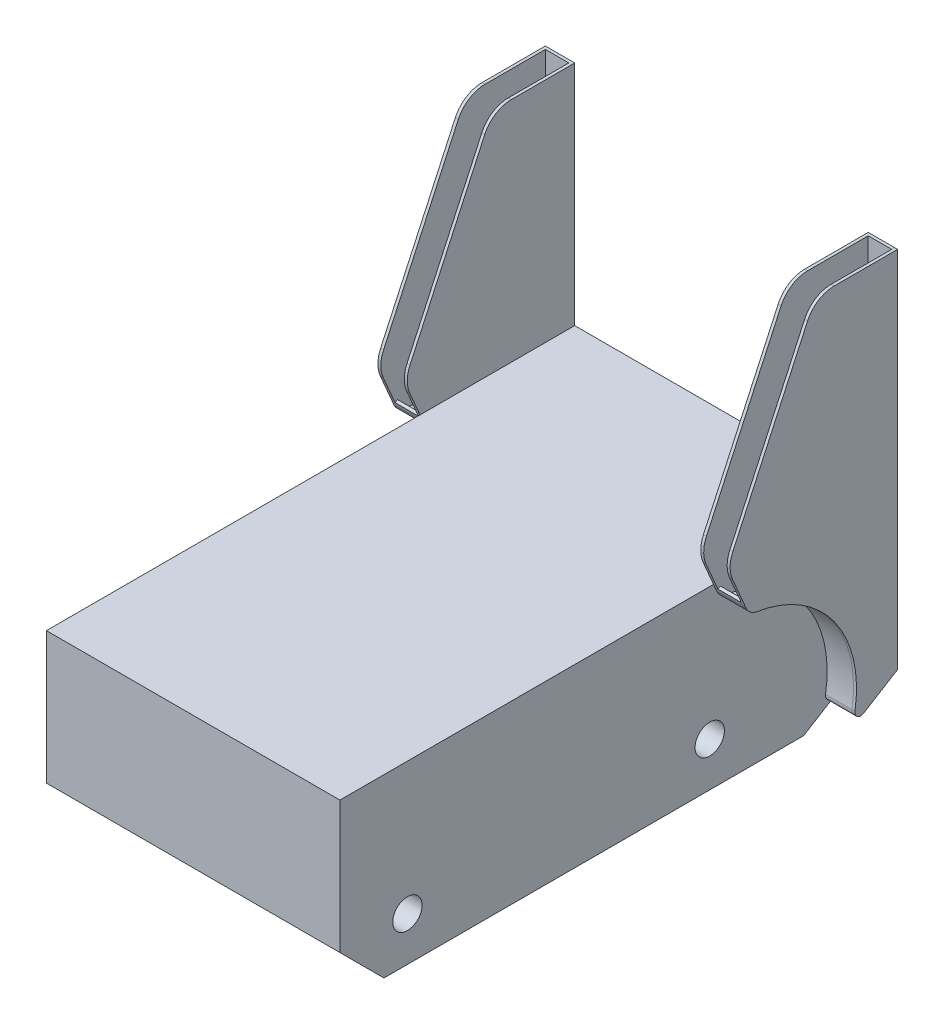
SolidWorks part; units mm, degrees
ref_plane "Front Plane" through (0, 0, 0) normal (0, 0, 1) x (1, 0, 0)
ref_plane "Top Plane" through (0, 0, 0) normal (0, 1, 0) x (1, 0, 0)
ref_plane "Right Plane" through (0, 0, 0) normal (1, 0, 0) x (0, 0, -1)
sketch "Sketch2" plane through (0, 0, 0) normal (1, 0, 0) x (0, 0, -1)
  line L0 (-750, 0) -> (680, 0)
  line L1 (680, 0) -> (900, 135)
  line L2 (900, 135) -> (900, 600)
  line L3 (900, 600) -> (-900, 600)
  line L4 (-900, 600) -> (-900, 150)
  line L5 (-900, 150) -> (-750, 0)
  circle A0 centre (-670, 150) radius 50
  circle A1 centre (360, 150) radius 50
  point P13 (0, 0)
  point P14 (0, 0)
  point P15 (204.7634, 67.3548)
  dimension "D8" = 100
  dimension "D1" = 1800
  dimension "D2" = 150
  dimension "D3" = 150
  dimension "D4" = 220
  dimension "D5" = 135
  dimension "D6" = 600
  dimension "D7" = 900
  dimension "D9" = 1030
  dimension "D10" = 150
  dimension "D11" = 540
extrude "Boss-Extrude1" add sketch "Sketch2" along normal mid plane 1000
sketch "Sketch3" plane through (500, 0, 0) normal (1, 0, 0) x (0, 0, -1)
  line L0 (900, 135) -> (900, 1375)
  line L1 (900, 1375) -> (684.0464, 1375)
  line L2 (593.213, 1316.8244) -> (338.5875, 763.8338)
  line L3 (337.5065, 682.6174) -> (383.6781, 574.8835)
  line L4 (900, 135) -> (784.8142, 64.3178)
  line L5 (680, 0) -> (900, 135) construction
  arc A0 (784.8142, 64.3178) -> (754.6227, 84.6326) centre (774.3539, 81.3643) cw
  arc A1 (754.6227, 84.6326) -> (421.8981, 545.1818) centre (360, 150) ccw
  circle A2 centre (360, 150) radius 50 construction
  arc A3 (383.6781, 574.8835) -> (421.8981, 545.1818) centre (429.6354, 594.5795) ccw
  arc A4 (684.0464, 1375) -> (593.213, 1316.8244) centre (684.0464, 1275) ccw
  arc A5 (338.5875, 763.8338) -> (337.5065, 682.6174) centre (429.421, 722.0093) ccw
  point P12 (0, 0)
  point P17 (395, 548.4658)
  point P20 (620, 1375)
  point P23 (320, 723.4658)
  dimension "D5" = 20
  dimension "D6" = 400
  dimension "D8" = 50
  dimension "D9" = 100
  dimension "D10" = 100
  dimension "D1" = 1240
  dimension "D2" = 280
  dimension "D3" = 175
  dimension "D4" = 75
  dimension "D7" = 35
extrude "Boss-Extrude2" add sketch "Sketch3" along normal blind 10 separate body
sketch "Sketch4" plane through (510, 0, 0) normal (1, 0, 0) x (0, 0, -1)
  line L0 (372.9139, 600) -> (383.6781, 574.8835) construction
  line L1 (382.1054, 603.9392) -> (392.8696, 578.8227) construction
  line L2 (377.6282, 589) -> (386.8197, 592.9392)
  line L3 (900, 135) -> (900, 1375) construction
  line L4 (784.8142, 64.3178) -> (900, 135) construction
  line L5 (372.9139, 600) -> (383.6781, 574.8835) construction
  line L6 (377.6282, 589) -> (383.6781, 574.8835)
  line L7 (784.8142, 64.3178) -> (900, 135)
  line L8 (900, 135) -> (900, 1375)
  line L9 (386.8197, 592.9392) -> (392.8696, 578.8227)
  line L10 (779.584, 72.841) -> (890, 140.5963)
  line L11 (890, 140.5963) -> (890, 1375)
  line L12 (890, 1375) -> (900, 1375)
  line L13 (900, 600) -> (-900, 600) construction
  arc A2 (754.6227, 84.6326) -> (784.8142, 64.3178) centre (774.3539, 81.3643) ccw construction
  arc A3 (754.6227, 84.6326) -> (421.8981, 545.1818) centre (360, 150) ccw construction
  arc A4 (383.6781, 574.8835) -> (421.8981, 545.1818) centre (429.6354, 594.5795) ccw construction
  arc A5 (383.6781, 574.8835) -> (421.8981, 545.1818) centre (429.6354, 594.5795) ccw
  arc A6 (754.6227, 84.6326) -> (421.8981, 545.1818) centre (360, 150) ccw
  arc A7 (754.6227, 84.6326) -> (784.8142, 64.3178) centre (774.3539, 81.3643) ccw
  arc A8 (392.8696, 578.8227) -> (423.4456, 555.0613) centre (429.6354, 594.5795) ccw
  arc A9 (764.4883, 82.9984) -> (423.4456, 555.0613) centre (360, 150) ccw
  arc A10 (764.4883, 82.9984) -> (779.584, 72.841) centre (774.3539, 81.3643) ccw
  dimension "D2" = 11
  dimension "D1" = 10
extrude "Boss-Extrude3" add sketch "Sketch4" along normal blind 80
extrude "Boss-Extrude4" add sketch "Sketch3<2>" along normal blind 10 from offset 90
sketch "Sketch3<2>" plane through (500, 0, 0) normal (1, 0, 0) x (0, 0, -1) same geometry as "Sketch3"
mirror "Mirror1" about plane through (0, 0, 0) normal (1, 0, 0) of "Boss-Extrude4", "Boss-Extrude2", "Boss-Extrude3"
